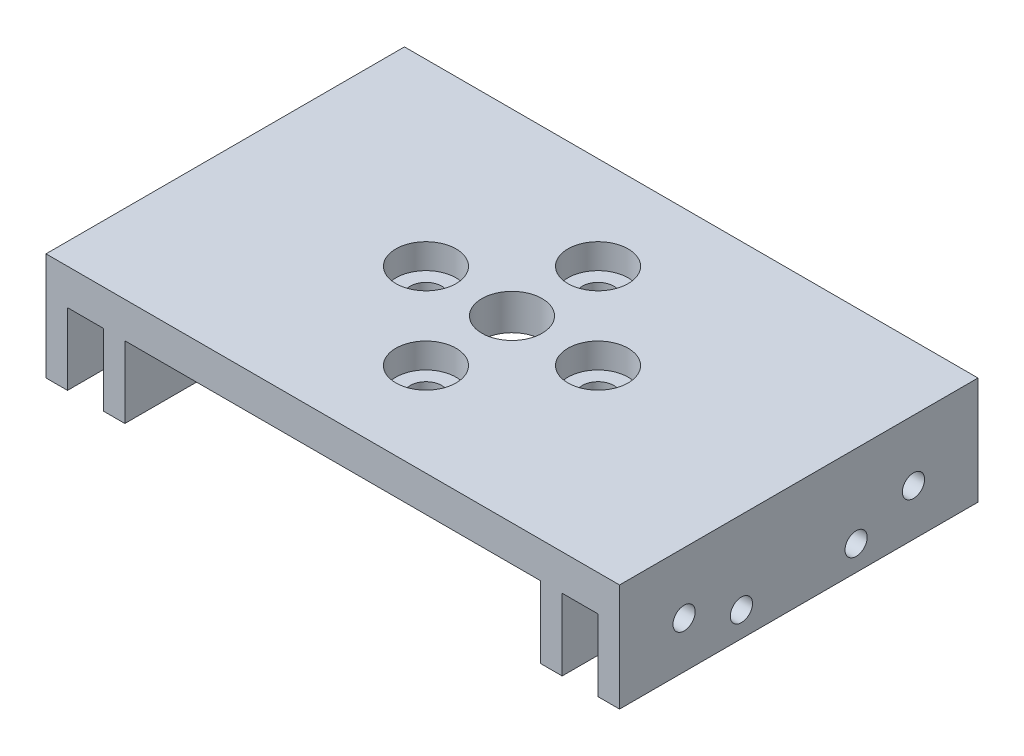
SolidWorks part; units mm, degrees
ref_plane "Front Plane" through (0, 0, 0) normal (0, 0, 1) x (1, 0, 0)
ref_plane "Top Plane" through (0, 0, 0) normal (0, 1, 0) x (1, 0, 0)
ref_plane "Right Plane" through (0, 0, 0) normal (1, 0, 0) x (0, 0, -1)
sketch "Sketch4" plane through (0, 0, 0) normal (0, 1, 0) x (1, 0, 0)
  line L1 (-40, 25) -> (40, 25)
  line L2 (-40, 25) -> (-40, -25)
  line L3 (-40, -25) -> (40, -25)
  line L4 (40, 25) -> (40, -25)
  line L5 (-40, 25) -> (40, -25) construction
  line L6 (-40, -25) -> (40, 25) construction
  circle A1 centre (0, 0) radius 4.2
  circle A2 centre (0, 0) radius 12 construction
  circle A3 centre (0, -12) radius 2.2
  circle A4 centre (-12, 0) radius 2.2
  circle A5 centre (0, 12) radius 2.2
  circle A6 centre (12, 0) radius 2.2
  point P18 (0, 0)
  dimension "D1" = 4
extrude "Boss-Extrude3" add sketch "Sketch4" against normal blind 5
sketch "Sketch16" plane through (0, -5, 0) normal (0, -1, 0) x (1, 0, 0)
  line L0 (0, 0) -> (32, 0) construction
  line L6 (0, 0) -> (-32, 0) construction
  line L12 (-32, -25) -> (-32, 25)
  line L13 (-32, 25) -> (-29, 25)
  line L14 (-29, 25) -> (-29, -25)
  line L15 (-29, -25) -> (-32, -25)
  line L16 (-32, 0) -> (-37, 0) construction
  line L17 (-37, -25) -> (-37, 25)
  line L18 (-37, 25) -> (-40, 25)
  line L19 (-40, 25) -> (-40, -25)
  line L20 (-40, -25) -> (-37, -25)
  line L21 (32, -25) -> (32, 25)
  line L22 (32, 25) -> (29, 25)
  line L23 (29, 25) -> (29, -25)
  line L24 (29, -25) -> (32, -25)
  line L25 (32, 0) -> (37, 0) construction
  line L26 (37, -25) -> (37, 25)
  line L27 (37, 25) -> (40, 25)
  line L28 (40, 25) -> (40, -25)
  line L29 (40, -25) -> (37, -25)
  point P7 (-32, 0)
  point P14 (-37, 0)
  point P19 (32, 0)
  point P25 (37, 0)
extrude "Boss-Extrude4" add sketch "Sketch16" along normal blind 10
sketch "Sketch17" plane through (-40, 0, 0) normal (-1, 0, 0) x (0, 0, 1)
  line L0 (-25, -15) -> (-25, -11.5) construction
  line L1 (-25, -15) -> (-25, 0) construction
  line L2 (-25, -11.5) -> (-8, -11.5) construction
  line L3 (-8, -11.5) -> (8, -11.5) construction
  line L4 (-16, -8.5) -> (16, -8.5) construction
  line L5 (-25, 0) -> (-25, -8.5) construction
  line L6 (-25, -8.5) -> (-16, -8.5) construction
  circle A0 centre (-16, -8.5) radius 1.55
  circle A1 centre (-8, -11.5) radius 1.55
  circle A3 centre (8, -11.5) radius 1.55
  circle A5 centre (16, -8.5) radius 1.55
extrude "Cut-Extrude10" cut sketch "Sketch17" against normal up to surface (11 mm away) up to face at (-29, -10, 0)
sketch "Sketch18" plane through (40, 0, 0) normal (1, 0, 0) x (0, 0, -1)
  line L0 (-25, -15) -> (-25, -11.5) construction
  line L1 (-25, -11.5) -> (-8, -11.5) construction
  line L2 (-8, -11.5) -> (8, -11.5) construction
  line L3 (8, -11.5) -> (-8, -11.5) construction
  line L4 (-25, 0) -> (-25, -8.5) construction
  line L5 (-25, -15) -> (-25, 0) construction
  line L6 (-25, -8.5) -> (-16, -8.5) construction
  line L10 (16, -8.5) -> (-16, -8.5) construction
  circle A0 centre (-8, -11.5) radius 1.55
  circle A1 centre (8, -11.5) radius 1.55
  circle A2 centre (16, -8.5) radius 1.55
  circle A3 centre (-16, -8.5) radius 1.55
extrude "Cut-Extrude11" cut sketch "Sketch18" against normal up to surface (11 mm away) up to face at (29, -10, 0)
sketch "Sketch19" plane through (0, 0, 0) normal (0, 1, 0) x (1, 0, 0)
  circle A0 centre (0, 0) radius 12 construction
  circle A1 centre (0, 12) radius 4.2
  circle A2 centre (12, 0) radius 4.2
  circle A3 centre (0, -12) radius 4.2
  circle A4 centre (-12, 0) radius 4.2
  point P14 (0, 0)
  dimension "D1" = 4
extrude "Cut-Extrude12" cut sketch "Sketch19" against normal blind 3.5
